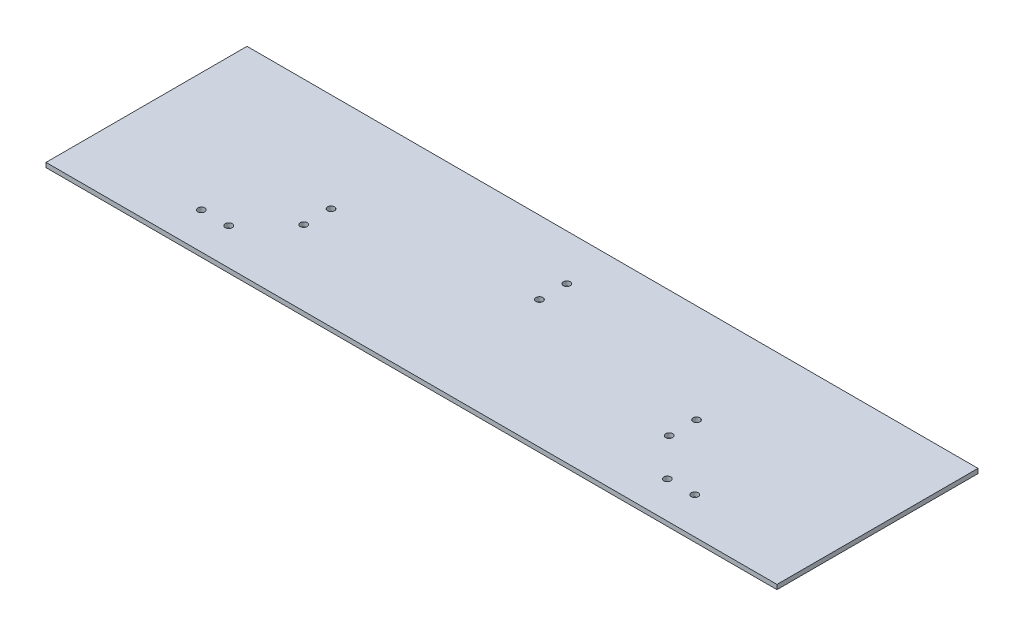
SolidWorks part; units mm, degrees
material "Lexan"
ref_plane "Front Plane" through (0, 0, 0) normal (0, 0, 1) x (1, 0, 0)
ref_plane "Top Plane" through (0, 0, 0) normal (0, 1, 0) x (1, 0, 0)
ref_plane "Right Plane" through (0, 0, 0) normal (1, 0, 0) x (0, 0, -1)
sketch "Sketch1" plane through (0, 0, 0) normal (0, 1, 0) x (1, 0, 0)
  line L1 (0, 0) -> (508, 0)
  line L2 (0, 0) -> (0, -139.7)
  line L3 (0, -139.7) -> (508, -139.7)
  line L4 (508, 0) -> (508, -139.7)
  dimension "D1" = 508
  dimension "D2" = 139.7
extrude "Boss-Extrude1" add sketch "Sketch1" along normal blind 3.175
sketch "Sketch2" plane through (0, 3.175, 0) normal (0, 1, 0) x (1, 0, 0)
  line L0 (0, 0) -> (0, -139.7) construction
  line L1 (0, -139.7) -> (508, -139.7) construction
  line L2 (508, 0) -> (0, 0) construction
  line L3 (508, -139.7) -> (508, 0) construction
  circle A0 centre (82.55, -114.3) radius 2.413
  circle A1 centre (101.6, -114.3) radius 2.413
  circle A2 centre (127, -87.63) radius 2.413
  circle A3 centre (127, -68.58) radius 2.413
  circle A4 centre (254, -31.75) radius 2.413
  circle A5 centre (254, -50.8) radius 2.413
  circle A6 centre (425.45, -114.3) radius 2.413
  circle A7 centre (406.4, -114.3) radius 2.413
  circle A8 centre (381, -87.63) radius 2.413
  circle A9 centre (381, -68.58) radius 2.413
  point P26 (0, 0)
  point P27 (0, 0)
  dimension "D3" = 4.826
  dimension "D4" = 4.826
  dimension "D9" = 4.826
  dimension "D10" = 4.826
  dimension "D13" = 4.826
  dimension "D14" = 4.826
  dimension "D16" = 4.826
  dimension "D17" = 4.826
  dimension "D22" = 4.826
  dimension "D23" = 19.05
  dimension "D24" = 4.826
  dimension "D1" = 82.55
  dimension "D2" = 25.4
  dimension "D5" = 19.05
  dimension "D6" = 52.07
  dimension "D7" = 25.4
  dimension "D8" = 19.05
  dimension "D11" = 31.75
  dimension "D12" = 127
  dimension "D15" = 19.05
  dimension "D18" = 82.55
  dimension "D19" = 19.05
  dimension "D20" = 52.07
  dimension "D21" = 25.4
  dimension "D25" = 25.4
  dimension "D26" = 71.12
  dimension "D27" = 25.4
  dimension "D28" = 25.4
  dimension "D29" = 127
extrude "Cut-Extrude1" cut sketch "Sketch2" against normal up to surface (3.175 mm away) up to face at (254, 0, 69.85)
